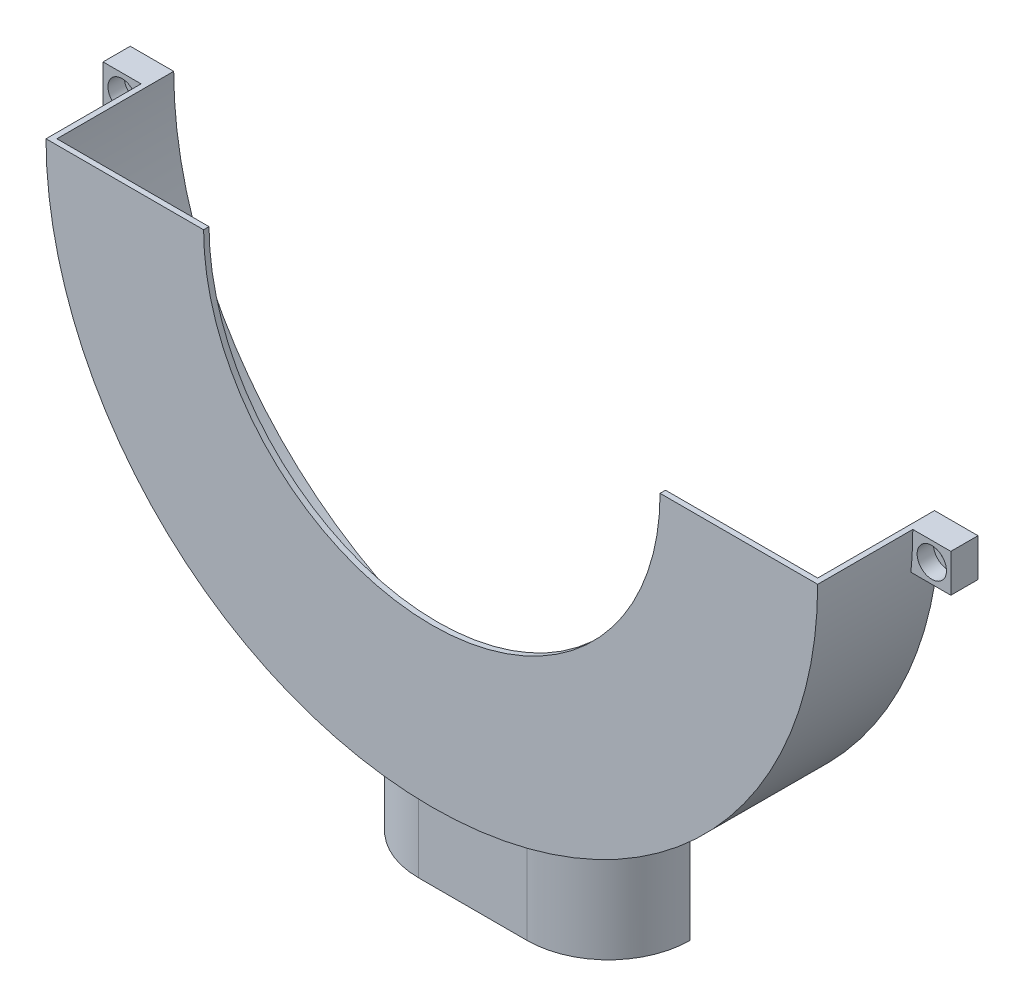
SolidWorks part; units mm, degrees
ref_plane "Front Plane" through (0, 0, 0) normal (0, 0, 1) x (1, 0, 0)
ref_plane "Top Plane" through (0, 0, 0) normal (0, 1, 0) x (1, 0, 0)
ref_plane "Right Plane" through (0, 0, 0) normal (1, 0, 0) x (0, 0, -1)
sketch "Sketch1" plane through (0, 0, 0) normal (0, 0, 1) x (1, 0, 0)
  line L0 (-71, 0) -> (71, 0)
  circle A0 centre (0, 0) radius 71
  circle A1 centre (0, 0) radius 70
  point P7 (0, 0)
extrude "Boss-Extrude1" add sketch "Sketch1" along normal blind 21.5 contours A1 L0 A0 region at (70.5, -1.5876, 0)
sketch "Sketch2" plane through (0, 0, 21.5) normal (0, 0, 1) x (1, 0, 0)
  line L0 (-80, 0) -> (80, 0)
  circle A0 centre (0, 0) radius 80
  circle A1 centre (0, 0) radius 42
  point P7 (0, 0)
  arc M1 (70, 0) -> (-70, 0) centre (0, 0) cw
  line M2 (-70, 0) -> (-71, 0)
  arc M3 (-71, 0) -> (71, 0) centre (0, 0) ccw
  line M4 (71, 0) -> (70, 0)
extrude "Boss-Extrude2" add sketch "Sketch2" along normal blind 1 contours M4 M1 M2 M3 | A1 L0 M1 region at (-70.5, -1.5876, 21.5) region at (-56, -1.5652, 21.5)
sketch "Sketch3" plane through (0, 0, 0) normal (0, 0, -1) x (-1, 0, 0)
  line L0 (-25, -71) -> (25, -71)
  line L1 (25, -71) -> (25, -66.453)
  line L2 (-25, -71) -> (-25, -66.453)
  line L3 (-25, -71) -> (-25, -91)
  line L4 (-25, -91) -> (25, -91)
  line L5 (25, -91) -> (25, -71)
  arc A0 (-71, 0) -> (71, 0) centre (0, 0) ccw construction
  arc A1 (-71, 0) -> (71, 0) centre (0, 0) ccw
  point P6 (0, -71)
  arc M5 (-71, 0) -> (71, 0) centre (0, 0) ccw
extrude "Boss-Extrude3" add sketch "Sketch3" against normal blind 15 contours L2 L0 M5 | L0 L1 M5 | L4 L5 L0 L3 region at (18.7907, -69.6437, 0) region at (0, -81, 0) region at (-18.7907, -69.6437, 0)
sketch "Sketch8" plane through (0, 0, 0) normal (0, 0, -1) x (-1, 0, 0)
  line L0 (-78, -7) -> (-72.2291, -7)
  line L1 (-71, 0) -> (-78, 0)
  line L3 (-73, -7) -> (-78, -7)
  line L4 (-78, 0) -> (-78, -7)
  line L6 (-71, 0) -> (-78, -7) construction
  line L7 (-73, -7) -> (-69.6491, -7)
  line L8 (-69.6491, -7) -> (-71, 0)
  line L9 (0, -70) -> (0, 0) construction
  line L10 (71, 0) -> (78, -7) construction
  line L11 (69.6491, -7) -> (71, 0)
  line L12 (73, -7) -> (69.6491, -7)
  line L13 (78, 0) -> (78, -7)
  line L14 (73, -7) -> (78, -7)
  line L15 (71, 0) -> (78, 0)
  line L16 (78, -7) -> (72.2291, -7)
  circle A0 centre (-74.5, -3.5) radius 1.6
  arc A1 (-70, 0) -> (70, 0) centre (0, 0) ccw construction
  circle A2 centre (74.5, -3.5) radius 1.6
  dimension "D1" = 7
  dimension "D2" = 7
extrude "Boss-Extrude5" add sketch "Sketch8" against normal blind 5 contours L11 L6 A0 L0 | L6 L1 L4 A0 | L0 L11 | L14 L12 L11 L15 L13 | A2 region at (77.891, -3.5, 0)
sketch "Sketch10" plane through (0, 0, 5) normal (0, 0, 1) x (1, 0, 0)
  circle A0 centre (74.5, -3.5) radius 2.7
  circle A1 centre (-74.5, -3.5) radius 2.6
extrude "Cut-Extrude5" cut sketch "Sketch10" against normal blind 3
fillet "Fillet2" radius 15 2 edges at (-25, -78.7265, 15) (25, -78.7265, 15)
sketch "Sketch11" plane through (0, -91, 0) normal (0, -1, 0) x (1, 0, 0)
  line L0 (10, 12) -> (-10, 12)
  line L1 (-21.619, 3) -> (21.619, 3)
  line L2 (10, 15) -> (-10, 15)
  line L3 (-25, 0) -> (25, 0)
  line L4 (10, 15) -> (-10, 15)
  line L5 (-25, 0) -> (25, 0)
  line L6 (21.619, 3) -> (21.619, 0)
  line L7 (-21.619, 3) -> (-21.619, 0)
  arc A0 (-10, 12) -> (-21.619, 3) centre (-10, 0) ccw
  arc A1 (21.619, 3) -> (10, 12) centre (10, 0) ccw
  arc A2 (-10, 15) -> (-25, 0) centre (-10, 0) ccw
  arc A3 (25, 0) -> (10, 15) centre (10, 0) ccw
  arc A4 (-10, 15) -> (-25, 0) centre (-10, 0) ccw
  arc A5 (25, 0) -> (10, 15) centre (10, 0) ccw
  dimension "D1" = 0
  dimension "D2" = 3
extrude "Cut-Extrude7" cut sketch "Sketch11" against normal blind 20 contours L1 L7 L5 L6 | L1 A1 L0 A0 region at (0, -91, 7.1524) region at (0, -91, 1.5)
